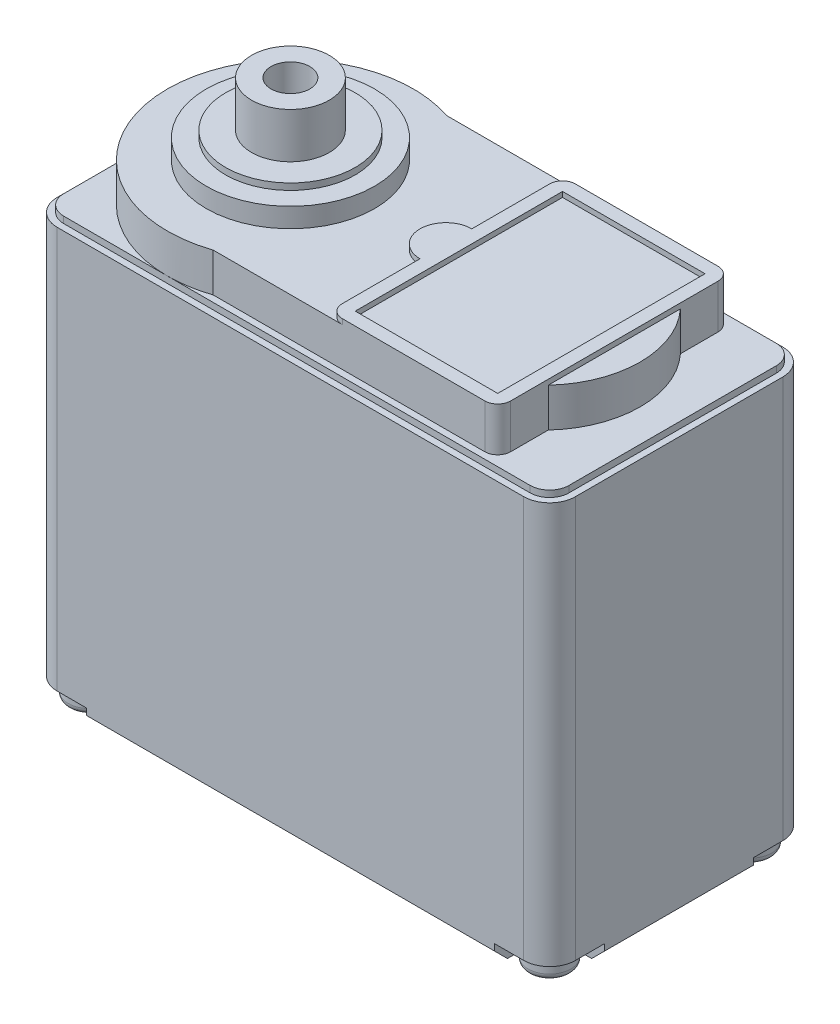
SolidWorks part; units mm, degrees
ref_plane "Спереди" through (0, 0, 0) normal (0, 0, 1) x (1, 0, 0)
ref_plane "Сверху" through (0, 0, 0) normal (0, 1, 0) x (1, 0, 0)
ref_plane "Справа" through (0, 0, 0) normal (1, 0, 0) x (0, 0, -1)
sketch "Эскиз1" plane through (0, 0, 0) normal (0, 1, 0) x (1, 0, 0)
  line L1 (-18, -10) -> (18, -10)
  line L2 (-20, -8) -> (-20, 8)
  line L3 (-18, 10) -> (18, 10)
  line L4 (20, -8) -> (20, 8)
  line L5 (-20, -10) -> (20, 10) construction
  line L6 (-20, 10) -> (20, -10) construction
  arc A0 (-18, -10) -> (-20, -8) centre (-18, -8) cw
  arc A1 (20, -8) -> (18, -10) centre (18, -8) cw
  arc A2 (20, 8) -> (18, 10) centre (18, 8) ccw
  arc A3 (-20, 8) -> (-18, 10) centre (-18, 8) cw
  point P0 (0, 0)
  dimension "D3" = 2
  dimension "D1" = 20
  dimension "D2" = 40
extrude "Бобышка-Вытянуть1" add sketch "Эскиз1" along normal blind 32.5
sketch "Эскиз2" plane through (0, 32.5, 0) normal (0, 1, 0) x (1, 0, 0)
  line L12 (-18, -9.5) -> (18, -9.5)
  line L13 (19.5, -8) -> (19.5, 8)
  line L14 (18, 9.5) -> (-18, 9.5)
  line L15 (-19.5, 8) -> (-19.5, -8)
  line L16 (-18, -9.5) -> (18, -9.5)
  line L17 (19.5, -8) -> (19.5, 8)
  line L18 (18, 9.5) -> (-18, 9.5)
  line L19 (-19.5, 8) -> (-19.5, -8)
  arc A10 (-19.5, -8) -> (-18, -9.5) centre (-18, -8) ccw
  arc A11 (18, -9.5) -> (19.5, -8) centre (18, -8) ccw
  arc A12 (19.5, 8) -> (18, 9.5) centre (18, 8) ccw
  arc A13 (-18, 9.5) -> (-19.5, 8) centre (-18, 8) ccw
  arc A14 (-19.5, -8) -> (-18, -9.5) centre (-18, -8) ccw
  arc A15 (18, -9.5) -> (19.5, -8) centre (18, -8) ccw
  arc A16 (19.5, 8) -> (18, 9.5) centre (18, 8) ccw
  arc A17 (-18, 9.5) -> (-19.5, 8) centre (-18, 8) ccw
  dimension "D1" = 0.5
extrude "Бобышка-Вытянуть2" add sketch "Эскиз2" along normal blind 0.5
sketch "Эскиз3" plane through (0, 0, 0) normal (0, -1, 0) x (1, 0, 0)
  line L0 (-21.9185, 5.75) -> (-17.75, 5.75)
  line L1 (-15.75, 7.75) -> (-15.75, 12.0926)
  line L2 (-20, -8) -> (-20, 8) construction
  line L3 (-18, 10) -> (18, 10) construction
  line L4 (-21.9185, 5.75) -> (-21.9185, 12.0926)
  line L6 (-15.75, 12.0926) -> (-21.9185, 12.0926)
  line L8 (15.75, 12.0926) -> (21.9185, 12.0926)
  line L9 (21.9185, 5.75) -> (21.9185, 12.0926)
  line L10 (15.75, 7.75) -> (15.75, 12.0926)
  line L11 (21.9185, 5.75) -> (17.75, 5.75)
  line L12 (21.9185, -5.75) -> (17.75, -5.75)
  line L13 (15.75, -7.75) -> (15.75, -12.0926)
  line L14 (21.9185, -5.75) -> (21.9185, -12.0926)
  line L15 (15.75, -12.0926) -> (21.9185, -12.0926)
  line L16 (-15.75, -12.0926) -> (-21.9185, -12.0926)
  line L17 (-21.9185, -5.75) -> (-21.9185, -12.0926)
  line L18 (-15.75, -7.75) -> (-15.75, -12.0926)
  line L19 (-21.9185, -5.75) -> (-17.75, -5.75)
  arc A0 (-15.75, 7.75) -> (-17.75, 5.75) centre (-17.75, 7.75) cw
  arc A1 (15.75, 7.75) -> (17.75, 5.75) centre (17.75, 7.75) ccw
  arc A2 (15.75, -7.75) -> (17.75, -5.75) centre (17.75, -7.75) cw
  arc A3 (-15.75, -7.75) -> (-17.75, -5.75) centre (-17.75, -7.75) ccw
  point P11 (-15.75, 5.75)
  point P21 (15.75, 5.75)
  point P34 (15.75, -5.75)
  point P35 (-15.75, -5.75)
  dimension "D3" = 2
  dimension "D1" = 4.25
  dimension "D2" = 4.25
extrude "Вырез-Вытянуть1" cut sketch "Эскиз3" against normal blind 1.5
chamfer "Фаска1" distance 1 angle 45 4 edges at (20, 0, 0) (0, 0, -10) (-20, 0, 0) (0, 0, 10)
sketch "Эскиз4" plane through (0, 33, 0) normal (0, 1, 0) x (1, 0, 0)
  line L1 (18, 9.5) -> (-18, 9.5) construction
  line L2 (-18, -9.5) -> (18, -9.5) construction
  line L3 (-19.5, 8) -> (-19.5, -8) construction
  line L4 (15, 8) -> (15, -8)
  line L5 (20, -8) -> (20, 8) construction
  line L6 (-6.9586, 9) -> (14, 9)
  line L7 (-6.9586, -9) -> (14, -9)
  line L8 (18, 10) -> (-18, 10) construction
  line L9 (-18, -10) -> (18, -10) construction
  arc A0 (-6.9586, 9) -> (-6.9586, -9) centre (-10, 0) ccw
  arc A1 (15, 8) -> (14, 9) centre (14, 8) ccw
  arc A2 (15, -8) -> (14, -9) centre (14, -8) cw
  dimension "D1" = 5
  dimension "D4" = 1
  dimension "D2" = 1
  dimension "D3" = 1
extrude "Бобышка-Вытянуть3" add sketch "Эскиз4" along normal blind 3
sketch "Эскиз5" plane through (0, 36, 0) normal (0, 1, 0) x (1, 0, 0)
  line L0 (15, -8) -> (15, 8) construction
  line L1 (15, -8) -> (15, 8)
  line L2 (2, 8) -> (2, 2)
  line L3 (14, 9) -> (3, 9)
  line L4 (2, -2) -> (2, -8)
  line L5 (14, -9) -> (3, -9)
  line L6 (3, -8) -> (14, -8)
  line L7 (14, 8) -> (3, 8)
  line L8 (3, 8) -> (3, -8)
  line L9 (14, -8) -> (14, 8)
  line L11 (2, 8) -> (2, -8) construction
  arc A0 (15, 8) -> (14, 9) centre (14, 8) ccw construction
  arc A1 (14, -9) -> (15, -8) centre (14, -8) ccw construction
  arc A2 (15, 8) -> (14, 9) centre (14, 8) ccw
  arc A3 (14, -9) -> (15, -8) centre (14, -8) ccw
  arc A4 (3, -9) -> (2, -8) centre (3, -8) cw
  arc A5 (3, 9) -> (2, 8) centre (3, 8) ccw
  arc A6 (2, 2) -> (2, -2) centre (2, 0) ccw
  arc M1 (15, 8) -> (14, 9) centre (14, 8) ccw
  line M2 (14, 9) -> (-6.9586, 9)
  line M4 (-6.9586, -9) -> (14, -9)
  arc M5 (14, -9) -> (15, -8) centre (14, -8) ccw
  line M6 (15, -8) -> (15, 8)
  dimension "D2" = 1
  dimension "D4" = 4
  dimension "D1" = 13
  dimension "D3" = 1
extrude "Бобышка-Вытянуть4" add sketch "Эскиз5" along normal blind 0.4 contours L11 A6 | L2 L11 L4 A4 A5 L9 L6 L8 L7 M4 M5 M6 M1 M2 region at (14.5501, 36, 8.5501) region at (1.1512, 36, 0)
sketch "Эскиз6" plane through (0, 36, 0) normal (0, 1, 0) x (1, 0, 0)
  circle A0 centre (-10, 0) radius 6.5
  dimension "D1" = 13
extrude "Бобышка-Вытянуть5" add sketch "Эскиз6" along normal blind 1.5
sketch "Эскиз7" plane through (0, 37.5, 0) normal (0, 1, 0) x (1, 0, 0)
  circle A0 centre (-10, 0) radius 5
  dimension "D1" = 10
extrude "Бобышка-Вытянуть6" add sketch "Эскиз7" along normal blind 0.5
sketch "Эскиз8" plane through (0, 38, 0) normal (0, 1, 0) x (1, 0, 0)
  circle A0 centre (-10, 0) radius 3
  circle A1 centre (-10, 0) radius 1.5
  dimension "D1" = 6
  dimension "D2" = 3
extrude "Бобышка-Вытянуть7" add sketch "Эскиз8" along normal blind 3.5
sketch "Эскиз9" plane through (0, 33, 0) normal (0, 1, 0) x (1, 0, 0)
  line L1 (20, -8) -> (20, 8) construction
  line L2 (14.5, 5.5902) -> (14.5, -5.5902)
  line L3 (19.5, -8) -> (19.5, 8) construction
  arc A0 (14.5, -5.5902) -> (14.5, 5.5902) centre (9.5, 0) ccw
  dimension "D1" = 15
  dimension "D2" = 10.5
  dimension "D3" = 5
extrude "Бобышка-Вытянуть8" add sketch "Эскиз9" along normal blind 3
ref_plane "Плоскость1" through (0, 26.5, 0) normal (0, -1, 0) x (-1, 0, 0)
sketch "Эскиз10" plane through (0, 26.5, 0) normal (0, -1, 0) x (-1, 0, 0)
  line L0 (-26.5, 6.4) -> (-25.6125, 6.4)
  line L1 (-24.6884, -9.5) -> (24.6884, -9.5)
  line L2 (-26.5, -7.6884) -> (-26.5, -6.4)
  line L3 (-24.6884, 9.5) -> (24.6884, 9.5)
  line L4 (26.5, -7.6884) -> (26.5, -6.4)
  line L5 (-26.5, -9.5) -> (26.5, 9.5) construction
  line L6 (-26.5, 9.5) -> (26.5, -9.5) construction
  line L7 (-26.5, 3.8) -> (-25.6125, 3.8)
  line L8 (-26.5, 6.4) -> (-26.5, 7.6884)
  line L9 (0, 0) -> (-7.7074, 0) construction
  line L10 (-7.7074, 0) -> (0, 0) construction
  line L11 (0, 0) -> (0, 4.5311) construction
  line L12 (26.5, 3.8) -> (25.6125, 3.8)
  line L13 (26.5, 6.4) -> (25.6125, 6.4)
  line L14 (26.5, 6.4) -> (26.5, 7.6884)
  line L15 (26.5, -3.8) -> (25.6125, -3.8)
  line L16 (26.5, -6.4) -> (25.6125, -6.4)
  line L17 (-26.5, -3.8) -> (-25.6125, -3.8)
  line L18 (-26.5, -6.4) -> (-25.6125, -6.4)
  line L19 (26.5, -3.8) -> (26.5, 3.8)
  line L20 (-26.5, -3.8) -> (-26.5, 3.8)
  arc A0 (26.5, 7.6884) -> (24.6884, 9.5) centre (24.6884, 7.6884) ccw
  arc A1 (26.5, -7.6884) -> (24.6884, -9.5) centre (24.6884, -7.6884) cw
  arc A2 (-24.6884, -9.5) -> (-26.5, -7.6884) centre (-24.6884, -7.6884) cw
  arc A3 (-26.5, 7.6884) -> (-24.6884, 9.5) centre (-24.6884, 7.6884) cw
  arc A4 (-25.6125, 3.8) -> (-25.6125, 6.4) centre (-23.9, 5.1) ccw
  arc A5 (25.6125, 3.8) -> (25.6125, 6.4) centre (23.9, 5.1) cw
  arc A6 (25.6125, -3.8) -> (25.6125, -6.4) centre (23.9, -5.1) ccw
  arc A7 (-25.6125, -3.8) -> (-25.6125, -6.4) centre (-23.9, -5.1) cw
  point P0 (0, 0)
  dimension "D3" = 1.8116
  dimension "D4" = 4.3
  dimension "D1" = 19
  dimension "D2" = 53
  dimension "D5" = 5.1
  dimension "D6" = 23.9
  dimension "D7" = 1.3
  dimension "D8" = 2.6
extrude "Бобышка-Вытянуть9" [suppressed] add sketch "Эскиз10" against normal blind 2.5
sketch "Эскиз11" [suppressed] plane through (0, 29, 0) normal (0, 1, 0) x (1, 0, 0)
  line L0 (26.5, 3.8) -> (26.5, -3.8) construction
  line L1 (22.9, 0.6) -> (18.0276, 0.6)
  line L2 (22.9, -0.6) -> (18.0276, -0.6)
  line L6 (18.0276, -0.6) -> (18.0276, 0.6)
  line L7 (0, 0) -> (0, 3.7247) construction
  line L8 (-22.9, 0.6) -> (-18.0276, 0.6)
  line L9 (-18.0276, -0.6) -> (-18.0276, 0.6)
  line L10 (-22.9, -0.6) -> (-18.0276, -0.6)
  arc A0 (22.9, -0.6) -> (22.9, 0.6) centre (22.9, 0) ccw
  arc A1 (2, 2) -> (2, -2) centre (2, 0) ccw construction
  arc A2 (-22.9, -0.6) -> (-22.9, 0.6) centre (-22.9, 0) cw
  point P4 (26.5, 0)
  dimension "D1" = 1.2
  dimension "D2" = 3.6
extrude "Бобышка-Вытянуть10" [suppressed] add sketch "Эскиз11" along normal blind 1
sketch "Эскиз12" plane through (0, 1.5, 0) normal (0, -1, 0) x (1, 0, 0)
  line L0 (0, 0) -> (0, 4.3916) construction
  line L1 (0, 0) -> (-4.3775, 0) construction
  line L2 (-18, 8) -> (-19, 8)
  line L3 (-19, 8) -> (-19, 7.5)
  line L4 (-19, 7.5) -> (-18, 7.5)
  line L5 (-17.5, 8) -> (-17.5, 9)
  line L6 (-17.5, 9) -> (-18, 9)
  line L7 (-18, 9) -> (-18, 8)
  line L8 (-17.5, 7.5) -> (-16.5, 7.5)
  line L9 (-16.5, 7.5) -> (-16.5, 8)
  line L10 (-16.5, 8) -> (-17.5, 8)
  line L11 (-18, 7.5) -> (-18, 6.5)
  line L12 (-18, 6.5) -> (-17.5, 6.5)
  line L13 (-17.5, 6.5) -> (-17.5, 7.5)
  line L14 (16.5, 7.5) -> (16.5, 8)
  line L15 (17.5, 7.5) -> (16.5, 7.5)
  line L16 (17.5, 6.5) -> (17.5, 7.5)
  line L17 (18, 6.5) -> (17.5, 6.5)
  line L18 (18, 7.5) -> (18, 6.5)
  line L19 (19, 7.5) -> (18, 7.5)
  line L20 (19, 8) -> (19, 7.5)
  line L21 (18, 8) -> (19, 8)
  line L22 (18, 9) -> (18, 8)
  line L23 (17.5, 9) -> (18, 9)
  line L24 (17.5, 8) -> (17.5, 9)
  line L25 (16.5, 8) -> (17.5, 8)
  line L26 (16.5, -8) -> (17.5, -8)
  line L27 (16.5, -7.5) -> (16.5, -8)
  line L28 (17.5, -7.5) -> (16.5, -7.5)
  line L29 (18, -6.5) -> (17.5, -6.5)
  line L30 (17.5, -6.5) -> (17.5, -7.5)
  line L31 (18, -7.5) -> (18, -6.5)
  line L32 (19, -7.5) -> (18, -7.5)
  line L33 (19, -8) -> (19, -7.5)
  line L34 (18, -8) -> (19, -8)
  line L35 (18, -9) -> (18, -8)
  line L36 (17.5, -9) -> (18, -9)
  line L37 (17.5, -8) -> (17.5, -9)
  line L38 (-17.5, -6.5) -> (-17.5, -7.5)
  line L39 (-18, -6.5) -> (-17.5, -6.5)
  line L40 (-18, -7.5) -> (-18, -6.5)
  line L41 (-19, -7.5) -> (-18, -7.5)
  line L42 (-19, -8) -> (-19, -7.5)
  line L43 (-18, -8) -> (-19, -8)
  line L44 (-16.5, -7.5) -> (-16.5, -8)
  line L45 (-17.5, -7.5) -> (-16.5, -7.5)
  line L46 (-16.5, -8) -> (-17.5, -8)
  line L47 (-17.5, -8) -> (-17.5, -9)
  line L48 (-18, -9) -> (-18, -8)
  line L49 (-17.5, -9) -> (-18, -9)
  circle A0 centre (-17.75, 7.75) radius 1.65
  circle A1 centre (17.75, 7.75) radius 1.65
  circle A2 centre (17.75, -7.75) radius 1.65
  circle A3 centre (-17.75, -7.75) radius 1.65
  dimension "D1" = 3.3
  dimension "D2" = 7.75
  dimension "D3" = 17.75
  dimension "D4" = 0.5
  dimension "D5" = 0.25
  dimension "D6" = 1.25
  dimension "D7" = 4
extrude "Бобышка-Вытянуть11" add sketch "Эскиз12" along normal blind 1.5
fillet "Скругление1" radius 0.5 4 edges at (17.75, 0, 9.4) (17.75, 0, -9.4) (-17.75, 0, -6.1) (-17.75, 0, 6.1)
